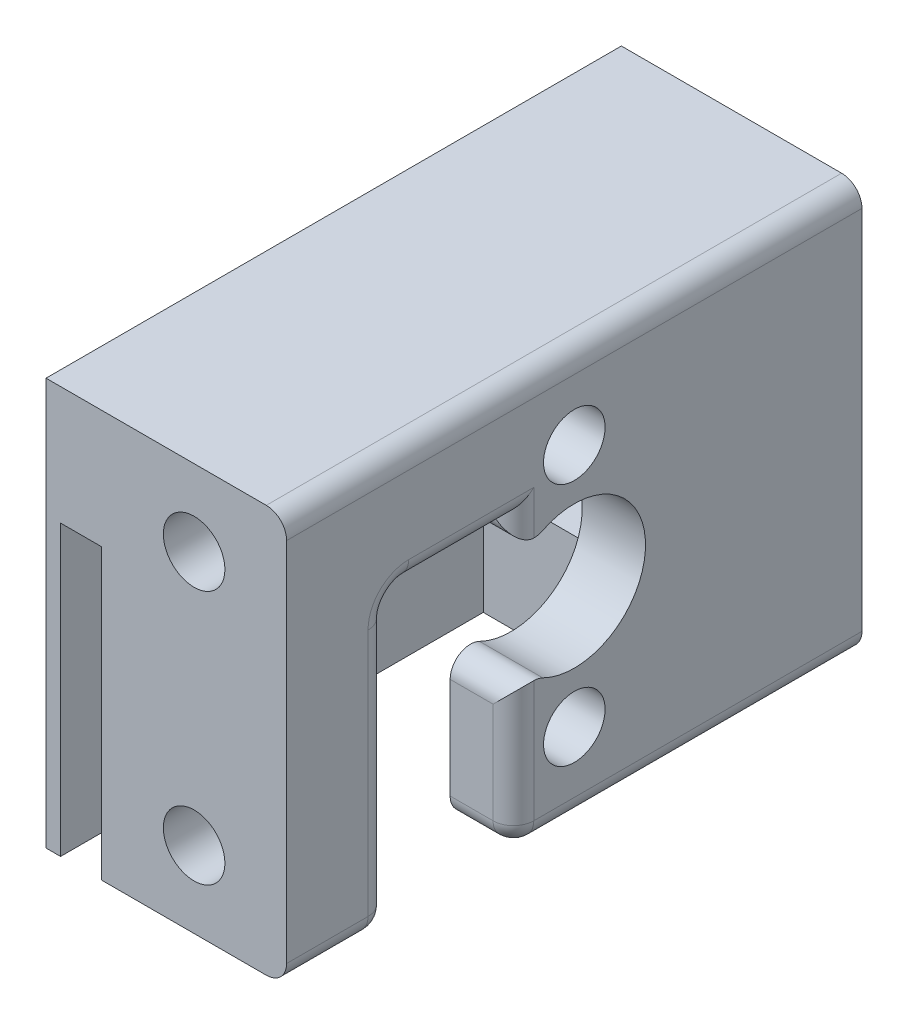
SolidWorks part; units mm, degrees
material "ABS"
ref_plane "X-Y Datum" through (0, 0, 0) normal (0, 0, 1) x (1, 0, 0)
ref_plane "X-Z Datum" through (0, 0, 0) normal (0, 1, 0) x (1, 0, 0)
ref_plane "Y-Z Datum" through (0, 0, 0) normal (1, 0, 0) x (0, 0, -1)
sketch "Sketch1" plane through (0, 0, 0) normal (0, 0, 1) x (1, 0, 0)
  line L1 (-11.825, 20) -> (11.825, 20)
  line L2 (-11.825, 20) -> (-11.825, -20)
  line L3 (-11.825, -20) -> (11.825, -20)
  line L4 (11.825, 20) -> (11.825, -20)
  line L5 (-11.825, 20) -> (11.825, -20) construction
  line L6 (-11.825, -20) -> (11.825, 20) construction
  point P0 (0, 0)
  dimension "D1" = 23.65
  dimension "D2" = 40
extrude "Boss-Extrude1" add sketch "Sketch1" along normal blind 56.55
sketch "Sketch2" plane through (0, 0, 56.55) normal (0, 0, 1) x (1, 0, 0)
  line L0 (-9.3955, -7.38) -> (-7.3635, -7.38) construction
  line L1 (-7.3635, -7.38) -> (-7.3635, 7.38) construction
  line L2 (-9.3955, 7.38) -> (-7.3635, 7.38) construction
  line L3 (-9.3955, 7.38) -> (-9.3955, -7.38) construction
  line L4 (-9.3955, -7.38) -> (-7.3635, -7.38)
  line L5 (-7.3635, -7.38) -> (-7.3635, 7.38)
  line L6 (-9.3955, 7.38) -> (-7.3635, 7.38)
  line L7 (-9.3955, 7.38) -> (-9.3955, -7.38)
  line L12 (-10.3955, -7.38) -> (-10.3955, -20)
  line L13 (-11.825, -20) -> (11.825, -20) construction
  line L14 (-7.3635, 8.38) -> (5.6045, 8.38)
  line L15 (5.6045, 8.38) -> (5.6045, -20)
  line L16 (-6.3635, -7.38) -> (-6.3635, 8.38) construction
  line L17 (-10.3955, 8.38) -> (-7.3635, 8.38)
  line L18 (-9.3955, 8.38) -> (-7.3635, 8.38) construction
  line L19 (-10.3955, 8.38) -> (-10.3955, -7.38)
  line L21 (-6.3635, -20) -> (-6.3635, 8.38)
  line L22 (-9.3955, 8.38) -> (-6.3635, 8.38) construction
  line L23 (-10.3955, 7.38) -> (-10.3955, -7.38) construction
  line M5 (-11.825, -20) -> (11.825, -20)
  dimension "D2" = 16
  dimension "D1" = 1
  dimension "D3" = 1
  dimension "D4" = 1
extrude "Cut-Extrude1" cut sketch "Sketch2" against normal through all contours L15 L12 M5 | L7 L6 L5 L4 | L6 L7 L4 L5 region at (-8.3795, 0, 56.55) region at (-8.3795, -7.8738, 56.55) region at (-0.3795, -5.81, 56.55)
sketch "Sketch3" plane through (11.825, 0, 0) normal (1, 0, 0) x (0, 0, -1)
  line L0 (-28.275, 20) -> (-28.275, -20) construction
  line L1 (-56.55, 20) -> (0, 20) construction
  line L2 (-56.55, -20) -> (0, -20) construction
  circle A0 centre (-28.275, 0) radius 7
  dimension "D1" = 14
extrude "Cut-Extrude2" cut sketch "Sketch3" against normal up to surface (6.2205 mm away) up to face at (5.6045, -5.81, 28.275)
sketch "Sketch6" plane through (11.825, 0, 0) normal (1, 0, 0) x (0, 0, -1)
  circle A0 centre (-28.275, -12) radius 2 construction
  circle A1 centre (-28.275, 12) radius 2 construction
  circle A2 centre (-28.275, -12) radius 2 construction
  circle A3 centre (-28.275, 12) radius 2 construction
  circle A4 centre (-28.275, 12) radius 3.025
  circle A5 centre (-28.275, -12) radius 3.025
  dimension "D1" = 6.05
extrude "Cut-Extrude4" cut sketch "Sketch6" against normal blind 8 contours A4 | A5 region at (11.825, 12, 28.275) region at (11.825, -12, 28.275)
sketch "Sketch4" plane through (0, 8.38, 0) normal (0, -1, 0) x (1, 0, 0)
  line L0 (-7.3635, 61.468) -> (-7.3635, 34.29) construction
  line L1 (-7.3635, 61.468) -> (-7.3635, 34.29) construction
  line L2 (-7.3635, 46.55) -> (5.6045, 46.55)
  line L3 (-6.3635, 61.468) -> (-6.3635, 34.29)
  line L4 (5.6045, 56.55) -> (-10.3955, 56.55)
  line L5 (-10.3955, 56.55) -> (-10.3955, 0)
  line L6 (-10.3955, 0) -> (5.6045, 0)
  line L7 (5.6045, 0) -> (5.6045, 56.55)
  line L8 (5.6045, 56.55) -> (-10.3955, 56.55)
  line L9 (-10.3955, 56.55) -> (-10.3955, 0)
  line L10 (-10.3955, 0) -> (5.6045, 0)
  line L11 (5.6045, 0) -> (5.6045, 56.55)
  line M5 (5.6045, 56.55) -> (-10.3955, 56.55)
  line M8 (5.6045, 0) -> (5.6045, 56.55)
  dimension "D2" = 10
  dimension "D1" = 0
  dimension "D3" = 1
extrude "Boss-Extrude2" add sketch "Sketch4" along normal up to surface (28.38 mm away) contours L1 L2 M8 M5 region at (-0.3795, 8.38, 51.55) up to face at (8.7147, -20, 28.275)
sketch "Sketch5" plane through (11.825, 0, 0) normal (1, 0, 0) x (0, 0, -1)
  line L0 (-32.258, 4.84) -> (-32.258, -4.84) construction
  line L1 (-32.258, 20) -> (-32.258, -20) construction
  line L2 (-56.55, -20) -> (0, -20) construction
  line L3 (-56.55, 20) -> (0, 20) construction
  line L4 (-56.55, 0) -> (0, 0)
  line L5 (0, 8.38) -> (-46.55, 8.38) construction
  line L6 (-34.258, 20) -> (-34.258, -20)
  line L7 (-46.55, -20) -> (-46.55, 8.38) construction
  line L8 (-46.55, -20) -> (-46.55, 8.38)
  line L9 (0, -20) -> (0, 20)
  line L10 (0, 20) -> (-56.55, 20)
  line L11 (-56.55, 20) -> (-56.55, -20)
  line L12 (-56.55, -20) -> (0, -20)
  line L13 (0, -20) -> (0, 20)
  line L14 (0, 20) -> (-56.55, 20)
  line L15 (-56.55, 20) -> (-56.55, -20)
  line L16 (-56.55, -20) -> (0, -20)
  line L17 (0, 8.38) -> (-46.55, 8.38)
  point P15 (-32.258, 0)
  circle M9 centre (-28.275, 0) radius 7
  line M13 (-56.55, -20) -> (0, -20)
  dimension "D1" = 0
  dimension "D2" = 2
extrude "Cut-Extrude3" cut sketch "Sketch5" against normal up to surface (6.2205 mm away) contours L6 L4 M9 M13 | L6 L4 M9 | L6 L17 L8 L4 M9 | L6 L4 M9 region at (11.825, -1.3769, 34.6674) region at (11.825, 1.3769, 34.6674) region at (11.825, 4.26, 40.5468) region at (11.825, -10.0887, 40.463) up to face at (5.6045, -15.025, 28.275)
fillet "Fillet5" radius 2 1 edges at (5.6045, 8.38, 17.129)
sketch "Sketch9" plane through (-10.3955, 0, 0) normal (1, 0, 0) x (0, 0, -1)
  line L1 (0, -20) -> (-15, -20)
  line L2 (0, -20) -> (0, -9)
  line L3 (0, -9) -> (-15, -9)
  line L4 (-15, -20) -> (-15, -9)
  dimension "D1" = 15
  dimension "D2" = 11
extrude "Boss-Extrude3" add sketch "Sketch9" along normal up to surface (16 mm away) up to face at (5.6045, -15.025, 28.275)
sketch "Sketch8" plane through (0, 0, 0) normal (0, 0, -1) x (-1, 0, 0)
  line L0 (0, 20) -> (0, 8.38) construction
  line L1 (-11.825, 20) -> (11.825, 20) construction
  line L2 (10.3955, 8.38) -> (-3.6045, 8.38) construction
  line L3 (-7.6296, 14.19) -> (7.6296, 14.19) construction
  line L4 (0, -20) -> (0, -9) construction
  line L5 (11.825, -20) -> (-11.825, -20) construction
  line L6 (-5.6045, -9) -> (10.3955, -9) construction
  line L7 (-4.1387, -14.5) -> (4.1387, -14.5) construction
  circle A0 centre (0, 14.19) radius 3.025
  circle A1 centre (0, -14.5) radius 3.025
  point P9 (0, 14.19)
  point P20 (0, -14.5)
  dimension "D1" = 6.05
extrude "Cut-Extrude6" cut sketch "Sketch8" against normal blind 8
sketch "Sketch7" plane through (0, 0, 56.55) normal (0, 0, 1) x (1, 0, 0)
  line L0 (2.7307, -20) -> (2.7307, 20) construction
  line L1 (-6.3635, -20) -> (11.825, -20) construction
  line L2 (11.825, 20) -> (-11.825, 20) construction
  line L3 (2.7307, 12.5) -> (2.7307, -12.5) construction
  circle A0 centre (2.7307, 12.5) radius 3.025
  circle A1 centre (2.7307, -12.5) radius 3.025
  point P11 (2.7307, 0)
  dimension "D1" = 6.05
  dimension "D2" = 25
extrude "Cut-Extrude5" cut sketch "Sketch7" against normal blind 8
fillet "Fillet4" radius 2 14 edges at (11.825, -11.8168, 34.258) (11.825, -20, 17.129) (8.7147, -3.6337, 34.258) (8.7147, 3.6337, 34.258) (11.825, -5.81, 46.55) (11.825, 6.0068, 34.258) (11.825, 8.38, 40.404) (11.825, 20, 28.275) (2.7308, -20, 46.55) (2.7308, 8.38, 46.55) (8.7147, -20, 34.258) (11.825, -20, 51.55) (5.6045, -14.5, 15) (5.6045, -9, 7.5)
sketch "Sketch10" [suppressed] plane through (0, 8.38, 0) normal (0, -1, 0) x (1, 0, 0)
  line L0 (-7.3635, 22.86) -> (-7.3635, -4.318) construction
  line L1 (-7.3635, 22.86) -> (-7.3635, -4.318) construction
  line L2 (-6.3635, 22.86) -> (-6.3635, -4.318)
  line L3 (5.6045, 0) -> (5.6045, 56.55) construction
  line L4 (5.6045, 0) -> (5.6045, 56.55)
  line L5 (5.6045, 10) -> (-6.3635, 10)
  line L6 (-10.3955, 0) -> (5.6045, 0) construction
  dimension "D2" = 10
  dimension "D1" = 1
extrude "Boss-Extrude4" [suppressed] add sketch "Sketch10" along normal up to surface (28.38 mm away) up to face at (-1.0626, -20, 24.9113)
sketch "Sketch11" [suppressed] plane through (11.825, 0, 0) normal (1, 0, 0) x (0, 0, -1)
  line L1 (-22.892, 8.38) -> (-22.892, -20)
  line L2 (-24.892, 4.84) -> (-24.892, -4.84) construction
  line L3 (-24.892, 4.84) -> (-24.892, -4.84) construction
  line L4 (-22.892, 4.84) -> (-22.892, -4.84) construction
  line L5 (-56.55, -20) -> (0, -20) construction
  line L6 (-10, -20) -> (-10, 8.38) construction
  line L7 (-10, -20) -> (-10, 8.38)
  line L8 (-10, 8.38) -> (-56.55, 8.38) construction
  line L9 (-10, 8.38) -> (-56.55, 8.38)
  dimension "D1" = 2
extrude "Cut-Extrude7" [suppressed] cut sketch "Sketch11" against normal up to surface (6.2205 mm away) up to face at (5.6045, -15.025, 28.275)
fillet "Fillet6" [suppressed] radius 2
sketch "Sketch12" [suppressed] plane through (-10.3955, 0, 0) normal (1, 0, 0) x (0, 0, -1)
  line L1 (-56.55, -20) -> (-41.55, -20)
  line L2 (-56.55, -20) -> (-56.55, -9)
  line L3 (-56.55, -9) -> (-41.55, -9)
  line L4 (-41.55, -20) -> (-41.55, -9)
  dimension "D1" = 15
  dimension "D2" = 11
extrude "Boss-Extrude5" [suppressed] add sketch "Sketch12" along normal up to surface (16 mm away) up to face at (5.6045, -15.025, 28.275)
sketch "Sketch13" [suppressed] plane through (0, 0, 0) normal (0, 0, -1) x (-1, 0, 0)
  circle A0 centre (-2.7307, -12.038) radius 3.025
  circle A1 centre (-2.7307, 12.962) radius 3.025
  point P0 (-2.7307, -12.038)
  point P1 (-2.7307, 12.962)
  dimension "D1" = 6.05
extrude "Cut-Extrude8" [suppressed] cut sketch "Sketch13" against normal blind 8
sketch "Sketch14" [suppressed] plane through (0, 0, 56.55) normal (0, 0, 1) x (1, 0, 0)
  circle A0 centre (0, -14.038) radius 3.025
  circle A1 centre (0, 14.652) radius 3.025
  point P0 (0, -14.038)
  point P1 (0, 14.652)
  dimension "D1" = 6.05
extrude "Cut-Extrude9" [suppressed] cut sketch "Sketch14" against normal blind 8
fillet "Fillet7" [suppressed] radius 2
